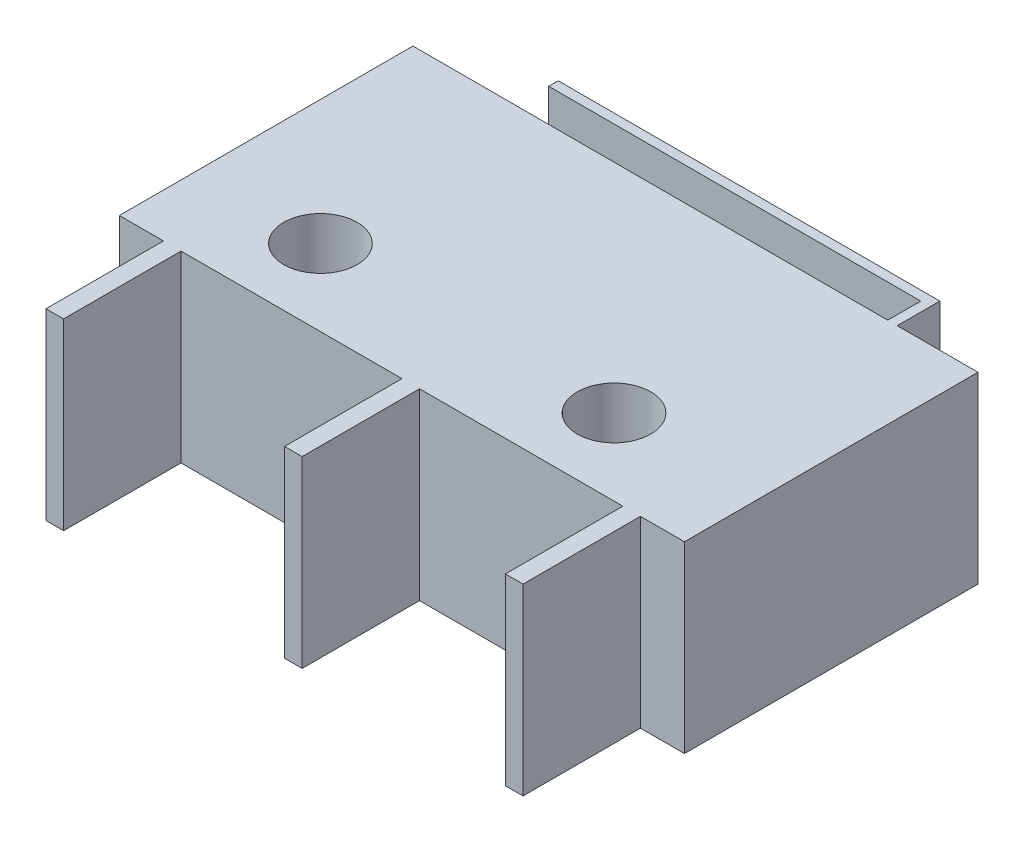
SolidWorks part; units mm, degrees
ref_plane "Front Plane" through (0, 0, 0) normal (0, 0, 1) x (1, 0, 0)
ref_plane "Top Plane" through (0, 0, 0) normal (0, 1, 0) x (1, 0, 0)
ref_plane "Right Plane" through (0, 0, 0) normal (1, 0, 0) x (0, 0, -1)
sketch "Sketch1" plane through (0, 0, 0) normal (0, 1, 0) x (1, 0, 0)
  line L1 (0.3138, 11.3771) -> (19.8718, 11.3771)
  line L2 (0.3138, 11.3771) -> (0.3138, 1.2171)
  line L3 (0.3138, 1.2171) -> (19.8718, 1.2171)
  line L4 (19.8718, 11.3771) -> (19.8718, 1.2171)
  line L5 (2.4474, -2.8469) -> (1.8378, -2.8469)
  line L6 (2.4474, -2.8469) -> (2.4474, 1.2171)
  line L7 (2.4474, 1.2171) -> (1.8378, 1.2171)
  line L8 (1.8378, -2.8469) -> (1.8378, 1.2171)
  line L9 (17.7382, 1.2171) -> (18.3478, 1.2171)
  line L10 (17.7382, 1.2171) -> (17.7382, -2.8469)
  line L11 (17.7382, -2.8469) -> (18.3478, -2.8469)
  line L12 (18.3478, 1.2171) -> (18.3478, -2.8469)
  line L13 (10.0928, 1.2171) -> (10.7024, 1.2171)
  line L14 (10.0928, 1.2171) -> (10.0928, -2.8469)
  line L15 (10.0928, -2.8469) -> (10.7024, -2.8469)
  line L16 (10.7024, 1.2171) -> (10.7024, -2.8469)
  line L17 (17.0778, 11.3771) -> (16.7476, 11.3771)
  line L18 (17.0778, 11.3771) -> (17.0778, 12.5201)
  line L19 (17.0778, 12.5201) -> (16.7476, 12.5201)
  line L20 (16.7476, 11.3771) -> (16.7476, 12.5201)
  line L21 (17.0778, 12.5201) -> (3.8698, 12.5201)
  line L22 (17.0778, 12.5201) -> (17.0778, 12.8503)
  line L23 (17.0778, 12.8503) -> (3.8698, 12.8503)
  line L24 (3.8698, 12.5201) -> (3.8698, 12.8503)
  dimension "D1" = 19.558
  dimension "D2" = 10.16
  dimension "D3" = 1.524
  dimension "D4" = 1.524
  dimension "D5" = 0.6096
  dimension "D6" = 4.064
  dimension "D7" = 4.064
  dimension "D8" = 4.064
  dimension "D9" = 0.6096
  dimension "D10" = 0.6096
  dimension "D11" = 2.794
  dimension "D12" = 0.3302
  dimension "D13" = 1.143
  dimension "D14" = 13.208
  dimension "D15" = 0.3302
extrude "Boss-Extrude1" add sketch "Sketch1" along normal blind 6.35 contours L12 L11 L10 L9 | L16 L15 L14 L13 | L6 L7 L8 L5 | L3 L4 L1 L2
sketch "Sketch2" plane through (0, 6.35, 0) normal (0, 1, 0) x (1, 0, 0)
  line L0 (19.8718, 11.3771) -> (19.8718, 1.2171) construction
  circle A0 centre (4.6318, 3.8584) radius 1.27
  circle A1 centre (14.7918, 3.8584) radius 1.27
  dimension "D1" = 10.16
  dimension "D2" = 2.54
  dimension "D3" = 2.54
  dimension "D4" = 5.08
extrude "Cut-Extrude1" cut sketch "Sketch2" against normal blind 6.35
extrude "Boss-Extrude2" add sketch "Sketch1<4>" along normal blind 6.35 contours L19 L20 L17 L18 | L21 L24 L23 L22
sketch "Sketch1<4>" plane through (0, 0, 0) normal (0, 1, 0) x (1, 0, 0) same geometry as "Sketch1"
